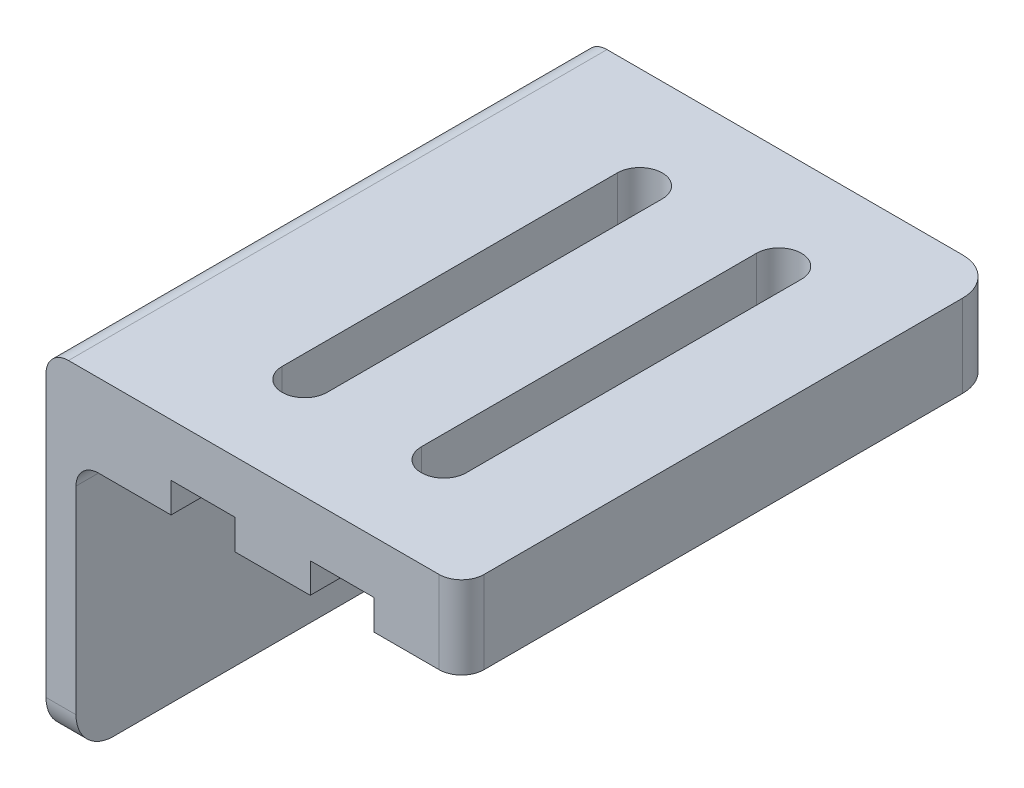
SolidWorks part; units mm, degrees
ref_plane "Front Plane" through (0, 0, 0) normal (0, 0, 1) x (1, 0, 0)
ref_plane "Top Plane" through (0, 0, 0) normal (0, 1, 0) x (1, 0, 0)
ref_plane "Right Plane" through (0, 0, 0) normal (1, 0, 0) x (0, 0, -1)
sketch "Sketch2" plane through (93.4, 0, 0) normal (-1, 0, 0) x (0, 0, 1)
  line L0 (5.2578, -173.8493) -> (-15.7255, -173.8493) construction
  line L1 (5.2578, -173.8493) -> (26.241, -173.8493) construction
  line L2 (5.2578, -173.8493) -> (5.2578, -155.7) construction
  line L3 (-15.7255, -189.7) -> (26.241, -189.7) construction
  line L4 (-15.7255, -189.9) -> (26.241, -189.9)
  line L5 (26.241, -193.9) -> (-15.7255, -193.9)
  line L6 (26.241, -193.9) -> (26.241, -144.5)
  line L8 (-15.7255, -193.9) -> (-15.7255, -144.5)
  line L9 (-15.7255, -155.5) -> (26.241, -155.5)
  line L10 (-15.7255, -144.5) -> (26.241, -144.5)
  line L11 (-15.7255, -155.7) -> (26.241, -155.7) construction
  circle A1 centre (5.2578, -173.8493) radius 4
  point P13 (0, 0)
  dimension "D1" = 8
  dimension "D2" = 18.1493
  dimension "D3" = 34
  dimension "D4" = 41.9666
  dimension "D5" = 0.2
  dimension "D6" = 4
  dimension "D7" = 155.7
  dimension "D8" = 15.7255
  dimension "D9" = 0.2
  dimension "D10" = 11
extrude "Boss-Extrude1" add sketch "Sketch2" along normal blind 4 from offset 0.2 contours L10 L8 L9 L6 | L9 L8 L4 L6 A1 | L8 L5 L6 L4 region at (93.4, -172.7, -15.1829) region at (93.4, -191.9, 5.2578) region at (93.4, -150, 5.2578)
extrude "Boss-Extrude2" add sketch "Sketch2<3>" along normal up to next and the other way blind 60.2 contours L10 L8 L9 L6 | L8 L5 L6 L4 region at (93.4, -191.9, 5.2578) region at (93.4, -150, 5.2578)
sketch "Sketch2<3>" plane through (93.4, 0, 0) normal (-1, 0, 0) x (0, 0, 1) same geometry as "Sketch2"
fillet "Fillet1" radius 3 5 edges at (153.6, -191.9, 26.241) (153.6, -191.9, -15.7255) (93.2, -155.5, 5.2578) (89.2, -193.9, 5.2578) (93.2, -189.9, 5.2578)
sketch "Sketch3" plane through (0, 0, 26.241) normal (0, 0, 1) x (1, 0, 0)
  line L0 (89.2, -144.5) -> (153.6, -144.5) construction
  line L1 (153.6, -144.5) -> (144.6, -144.5)
  line L2 (153.6, -144.5) -> (153.6, -155.7)
  line L3 (153.6, -155.7) -> (144.6, -155.7)
  line L4 (144.6, -144.5) -> (144.6, -155.7)
  dimension "D1" = 9
extrude "Cut-Extrude1" cut sketch "Sketch3" against normal blind 24.029
sketch "Sketch4" plane through (153.6, 0, 0) normal (1, 0, 0) x (0, 0, -1)
  line L0 (15.7255, -190.9) -> (15.7255, -144.5) construction
  line L1 (15.7255, -155.5) -> (-55.9337, -155.5)
  line L2 (15.7255, -155.5) -> (15.7255, -135.8096)
  line L3 (15.7255, -135.8096) -> (-55.9337, -135.8096)
  line L4 (-55.9337, -155.5) -> (-55.9337, -135.8096)
  line L9 (-9.6862, -150.8871) -> (-39.2974, -150.8871) construction
  line L10 (-9.6862, -140.5148) -> (-39.2974, -140.5148) construction
  line L12 (-9.6862, -142.5148) -> (-39.2974, -142.5148) construction
  line L13 (-9.6862, -148.8871) -> (-39.2974, -148.8871) construction
  arc A4 (-39.2974, -140.5148) -> (-39.2974, -150.8871) centre (-39.2974, -145.7009) ccw construction
  arc A5 (-9.6862, -150.8871) -> (-9.6862, -140.5148) centre (-9.6862, -145.7009) ccw construction
  arc A6 (-39.2974, -142.5148) -> (-39.2974, -148.8871) centre (-39.2974, -145.7009) ccw construction
  arc A7 (-9.6862, -148.8871) -> (-9.6862, -142.5148) centre (-9.6862, -145.7009) ccw construction
  circle A8 centre (-39.2974, -145.7009) radius 3.1862
  circle A9 centre (-9.6862, -145.7009) radius 3.1862
  dimension "D1" = 2
extrude "Boss-Extrude3" add sketch "Sketch4" against normal blind 4
fillet "Fillet2" radius 3 3 edges at (149.6, -144.5, -6.7568) (151.6, -135.8096, -15.7255) (151.6, -135.8096, 55.9337)
sketch "Sketch5" plane through (0, -144.5, 0) normal (0, 1, 0) x (1, 0, 0)
  line L0 (89.2, -26.241) -> (144.6, -26.241) construction
  line L1 (144.6, -26.241) -> (89.2, -26.241)
  line L2 (144.6, -26.241) -> (144.6, -56.0614)
  line L3 (144.6, -56.0614) -> (89.2, -56.0614)
  line L4 (89.2, -26.241) -> (89.2, -56.0614)
  line L6 (144.6, -2.212) -> (144.6, -26.241) construction
extrude "Boss-Extrude4" add sketch "Sketch5" against normal up to vertex (11 mm away) up to point (144.6, -155.5, 26.241)
fillet "Fillet3" radius 3 2 edges at (144.6, -150, 56.0614) (89.2, -144.5, 20.168)
sketch "Sketch7" plane through (0, 0, -15.7255) normal (0, 0, -1) x (-1, 0, 0)
  line L0 (-128.6778, -153.5) -> (-128.6778, -147.6036) construction
  line L1 (-153.6, -155.5) -> (-96.2, -155.5) construction
  line L2 (-119.4, -144.5) -> (-119.4, -155.5) construction
  line L3 (-132.9278, -155.5) -> (-124.4278, -155.5)
  line L4 (-132.9278, -155.5) -> (-132.9278, -151.5)
  line L5 (-132.9278, -151.5) -> (-124.4278, -151.5)
  line L6 (-124.4278, -155.5) -> (-124.4278, -151.5)
  line L7 (-132.9278, -155.5) -> (-124.4278, -151.5) construction
  line L8 (-132.9278, -151.5) -> (-124.4278, -155.5) construction
  line L9 (-92.2, -144.5) -> (-146.6, -144.5) construction
  line L10 (-105.8722, -151.5) -> (-114.3722, -155.5) construction
  line L11 (-105.8722, -155.5) -> (-114.3722, -151.5) construction
  line L12 (-110.1222, -153.5) -> (-110.1222, -147.6036) construction
  line L13 (-114.3722, -155.5) -> (-114.3722, -151.5)
  line L14 (-105.8722, -151.5) -> (-114.3722, -151.5)
  line L15 (-105.8722, -155.5) -> (-105.8722, -151.5)
  line L16 (-105.8722, -155.5) -> (-114.3722, -155.5)
  dimension "D1" = 4
  dimension "D2" = 8.5
extrude "Cut-Extrude2" cut sketch "Sketch7" against normal through all both and the other way through all
fillet "Fillet6" radius 2 1 edges at (144.6, -150, 2.212)
sketch "Sketch8" plane through (0, -144.5, 0) normal (0, 1, 0) x (1, 0, 0)
  line L0 (105.8722, 15.7255) -> (114.3722, 15.7255) construction
  line L1 (114.3722, 15.7255) -> (114.3722, -56.0614) construction
  line L2 (114.3722, -56.0614) -> (105.8722, -56.0614) construction
  line L3 (105.8722, -56.0614) -> (105.8722, 15.7255) construction
  line L8 (105.8722, 15.7255) -> (114.3722, 15.7255) construction
  line L9 (114.3722, 15.7255) -> (114.3722, -56.0614) construction
  line L10 (114.3722, -56.0614) -> (105.8722, -56.0614) construction
  line L11 (105.8722, -56.0614) -> (105.8722, 15.7255) construction
  line L16 (110.1222, 15.7255) -> (110.1222, -56.0614) construction
  line L17 (119.4, 15.7255) -> (119.4, -4.8632) construction
  line L18 (110.1222, 2.1725) -> (110.1222, -42.5084) construction
  line L19 (113.1222, 2.1725) -> (113.1222, -42.5084)
  line L20 (107.1222, 2.1725) -> (107.1222, -42.5084)
  line L21 (92.2, 15.7255) -> (146.6, 15.7255) construction
  line L22 (128.6778, 2.1725) -> (128.6778, -42.5084) construction
  line L23 (125.6778, 2.1725) -> (125.6778, -42.5084)
  line L24 (131.6778, 2.1725) -> (131.6778, -42.5084)
  arc A0 (113.1222, 2.1725) -> (107.1222, 2.1725) centre (110.1222, 2.1725) ccw
  arc A1 (107.1222, -42.5084) -> (113.1222, -42.5084) centre (110.1222, -42.5084) ccw
  arc A2 (125.6778, 2.1725) -> (131.6778, 2.1725) centre (128.6778, 2.1725) cw
  arc A3 (131.6778, -42.5084) -> (125.6778, -42.5084) centre (128.6778, -42.5084) cw
  point P14 (110.1222, -20.168)
  point P19 (128.6778, -20.168)
  point P20 (110.1222, -20.168)
  dimension "D1" = 6
extrude "Cut-Extrude3" cut sketch "Sketch8" against normal up to next
sketch "Sketch9" plane through (0, -135.8096, 0) normal (0, 1, 0) x (1, 0, 0)
  line L0 (144.6, -4.212) -> (144.6, -53.0614) construction
  line L1 (144.6, 47.1157) -> (144.6, -77.5818)
  line L2 (144.6, 47.1157) -> (190.1821, 46.6078)
  line L3 (190.1821, 46.6078) -> (185.5446, -56.6744)
  line L4 (185.5446, -56.6744) -> (144.6, -77.5818)
extrude "Cut-Extrude4" cut sketch "Sketch9" against normal through all both and the other way through all
fillet "Fillet7" radius 5 1 edges at (144.6, -150, -15.7255)
sketch "Sketch10" plane through (89.2, 0, 0) normal (-1, 0, 0) x (0, 0, 1)
  line L1 (26.241, -155.5) -> (56.0614, -155.5) construction
  line L2 (26.241, -189.9) -> (56.0614, -189.9)
  line L3 (26.241, -190.9) -> (26.241, -155.5) construction
  line L4 (26.241, -189.9) -> (26.241, -155.5)
  line L5 (26.241, -155.5) -> (56.0614, -155.5)
  line L6 (26.241, -189.9) -> (26.241, -186.9) construction
  line L7 (26.241, -193.9) -> (26.241, -189.9) construction
  line L10 (56.0614, -155.5) -> (56.0614, -189.9)
extrude "Boss-Extrude5" add sketch "Sketch10" against normal up to vertex (4 mm away) up to point (93.2, -186.9, 26.241)
sketch "Sketch11" plane through (0, 0, 26.241) normal (0, 0, 1) x (1, 0, 0)
  line L2 (93.2, -155.5) -> (93.2, -158.5)
  line L3 (96.2, -155.5) -> (93.2, -155.5)
  line L4 (93.2, -155.5) -> (93.2, -158.5)
  line L5 (96.2, -155.5) -> (93.2, -155.5)
  arc A1 (96.2, -155.5) -> (93.2, -158.5) centre (96.2, -158.5) ccw
  arc A3 (96.2, -155.5) -> (93.2, -158.5) centre (96.2, -158.5) ccw
  dimension "D1" = 0
extrude "Boss-Extrude6" add sketch "Sketch11" along normal up to surface (29.8204 mm away) up to face at (112.9852, -156.9786, 56.0614)
sketch "Sketch14" plane through (89.2, 0, 0) normal (-1, 0, 0) x (0, 0, 1)
  line L0 (5.2578, -168.4085) -> (5.2578, -179.2901) construction
  line L1 (9.2578, -168.4085) -> (9.2578, -179.2901)
  line L2 (1.2578, -168.4085) -> (1.2578, -179.2901)
  circle A0 centre (5.2578, -173.8493) radius 4 construction
  circle A1 centre (5.2578, -173.8493) radius 4 construction
  arc A2 (9.2578, -168.4085) -> (1.2578, -168.4085) centre (5.2578, -168.4085) ccw
  arc A3 (1.2578, -179.2901) -> (9.2578, -179.2901) centre (5.2578, -179.2901) ccw
  point P5 (5.2578, -173.8493)
extrude "Cut-Extrude5" cut sketch "Sketch14" against normal through all both and the other way through all
sketch "Sketch15" plane through (89.2, 0, 0) normal (-1, 0, 0) x (0, 0, 1)
  line L1 (61.4991, -189.9) -> (-17.2284, -189.9)
  line L2 (61.4991, -189.9) -> (61.4991, -203.7571)
  line L3 (61.4991, -203.7571) -> (-17.2284, -203.7571)
  line L4 (-17.2284, -189.9) -> (-17.2284, -203.7571)
extrude "Cut-Extrude6" cut sketch "Sketch15" against normal through all both and the other way through all
sketch "Sketch16" plane through (0, -189.9, 0) normal (0, -1, 0) x (1, 0, 0)
  line L0 (93.2, 26.241) -> (93.2, -15.7255) construction
  line L1 (93.2, 37.1066) -> (93.2, -15.7255)
  line L3 (93.2, 37.1066) -> (106.6333, 37.1066)
  line L4 (93.2, 37.1066) -> (93.2, -15.7255)
  line L5 (93.2, -15.7255) -> (106.6333, -15.7255)
  line L6 (106.6333, 37.1066) -> (106.6333, -15.7255)
  line M1 (89.2, -15.7255) -> (96.2, -15.7255)
  line M2 (96.2, -15.7255) -> (96.2, 26.241)
extrude "Cut-Extrude8" cut sketch "Sketch16" against normal up to next contours L1 M1 M2 region at (99.9167, -189.9, 10.6905)
fillet "Fillet8" radius 5 2 edges at (91.2, -189.9, 56.0614) (91.2, -189.9, -15.7255)
